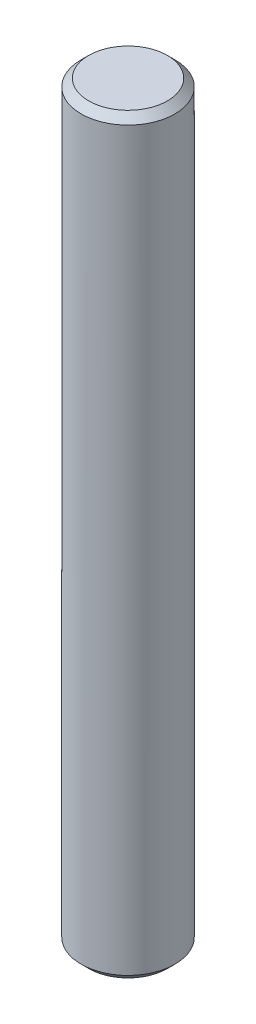
SolidWorks part; units mm, degrees
material "AISI 303 Stainless"
ref_plane "Front Plane" through (0, 0, 0) normal (0, 0, 1) x (1, 0, 0)
ref_plane "Top Plane" through (0, 0, 0) normal (0, 1, 0) x (1, 0, 0)
ref_plane "Right Plane" through (0, 0, 0) normal (1, 0, 0) x (0, 0, -1)
other "Configuration Table"
sketch "Sketch1" plane through (0, 0, 0) normal (0, 0, 1) x (1, 0, 0)
  line L0 (3.1712, 50.8) -> (0, 50.8)
  line L1 (0, 50.8) -> (0, 0)
  line L2 (0, 0) -> (3.1712, 0)
  line L3 (3.1712, 0) -> (3.1712, 50.8)
  line L4 (0, 50.8) -> (0, 0) construction
  dimension "D1" = 3.1712
  dimension "D2" = 50.8
revolve "Revolve1" add sketch "Sketch1" angle 360 about L4 reverse direction yes
chamfer "Chamfer1" distance 0.508 angle 45 1 edges at (0, 0, -3.1712)
chamfer "Chamfer2" distance 0.508 angle 45 1 edges at (0, 50.8, -3.1712)
ref_point "Point2"
ref_axis "Axis1" through (0, 53.34, 0) along (0, -1, 0)
